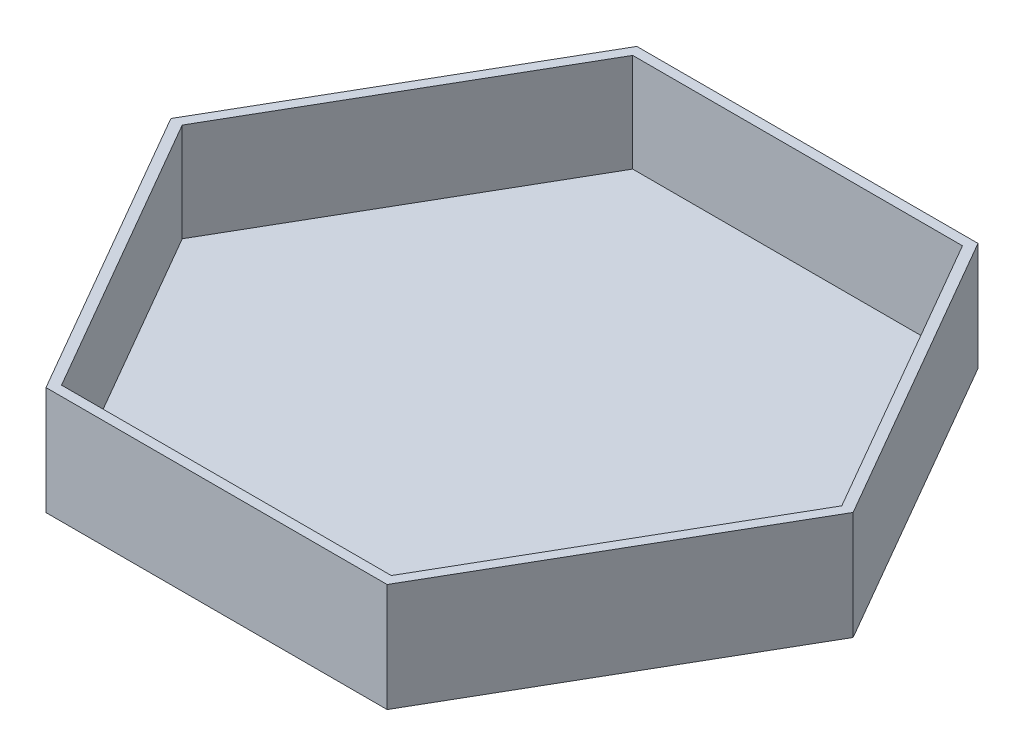
SolidWorks part; units mm, degrees
ref_plane "Front Plane" through (0, 0, 0) normal (0, 0, 1) x (1, 0, 0)
ref_plane "Top Plane" through (0, 0, 0) normal (0, 1, 0) x (1, 0, 0)
ref_plane "Right Plane" through (0, 0, 0) normal (1, 0, 0) x (0, 0, -1)
sketch "Sketch1" plane through (0, 0, 0) normal (0, 1, 0) x (1, 0, 0)
  line L1 (173.2051, 0) -> (86.6025, 150)
  line L2 (86.6025, 150) -> (-86.6025, 150)
  line L3 (-86.6025, 150) -> (-173.2051, 0)
  line L4 (-173.2051, 0) -> (-86.6025, -150)
  line L5 (-86.6025, -150) -> (86.6025, -150)
  line L6 (86.6025, -150) -> (173.2051, 0)
  circle A0 centre (0, 0) radius 150 construction
  dimension "D1" = 300
extrude "Boss-Extrude1" add sketch "Sketch1" along normal blind 55
shell "Shell1" thickness 5 removed face at (0, 55, 0)
